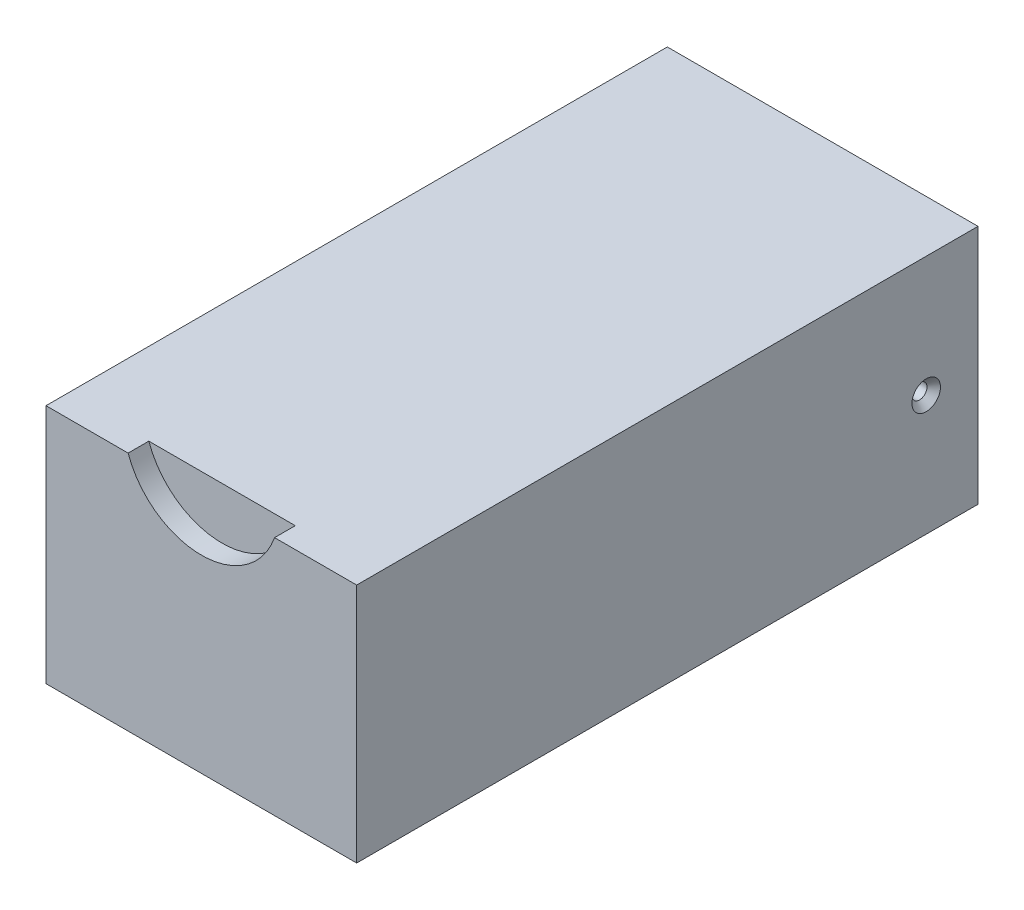
SolidWorks part; units mm, degrees
ref_plane "Plan de face" through (0, 0, 0) normal (0, 0, 1) x (1, 0, 0)
ref_plane "Plan de dessus" through (0, 0, 0) normal (0, 1, 0) x (1, 0, 0)
ref_plane "Plan de droite" through (0, 0, 0) normal (1, 0, 0) x (0, 0, -1)
sketch "Main-Sketch" plane through (0, 0, 0) normal (0, 0, 1) x (1, 0, 0)
  line L1 (-21.4947, -23.25) -> (38.5053, -23.25)
  line L2 (-21.4947, -23.25) -> (-21.4947, 23.25)
  line L3 (-21.4947, 23.25) -> (38.5053, 23.25)
  line L4 (38.5053, -23.25) -> (38.5053, 23.25)
  point P4 (-21.4947, 0)
  dimension "D1" = 60
  dimension "D2" = 46.5
extrude "Main-Extrusion" add sketch "Main-Sketch" along normal blind 120
ref_plane "Plan1" through (0, 0, 112) normal (0, 0, 1) x (1, 0, 0)
sketch "Main-Hole-Sketch" plane through (0, 0, 0) normal (0, 0, -1) x (-1, 0, 0)
  line L0 (-38.5053, -23.25) -> (-38.5053, 23.25) construction
  line L1 (-31.5053, 17.25) -> (14.4947, 17.25)
  line L2 (-31.5053, 17.25) -> (-31.5053, -17.25)
  line L3 (-31.5053, -17.25) -> (14.4947, -17.25)
  line L4 (14.4947, 17.25) -> (14.4947, -17.25)
  line L5 (-38.5053, 23.25) -> (21.4947, 23.25) construction
  line L6 (21.4947, 23.25) -> (21.4947, -23.25) construction
  line L7 (21.4947, -23.25) -> (-38.5053, -23.25) construction
  point P4 (-31.5053, 0)
  point P7 (-38.5053, 0)
  point P8 (-8.5053, 17.25)
  point P11 (-8.5053, 23.25)
  dimension "D1" = 34.5
  dimension "D2" = 46
  dimension "D3" = 7
  dimension "D4" = 7
  dimension "D5" = 6
  dimension "D6" = 6
extrude "Main-Hole" cut sketch "Main-Hole-Sketch" against normal up to surface (112 mm away) up to plane "Plan1"
hole_wizard "Fraisage pour vis à tête fraisée M2.51" positions "Esquisse4" profile "Esquisse3" countersink size "M2.5" standard "Ansi Metric" end condition through all
sketch "Esquisse4" plane through (38.5053, 0, 0) normal (1, 0, 0) x (0, 0, -1)
  line L0 (0, -23.25) -> (0, 23.25) construction
  line L1 (-112, 25.575) -> (-112, -25.575) construction
  point P0 (-10, 0)
  point P3 (0, 0)
  dimension "D2" = 102
sketch "Esquisse3" plane through (38.5053, 0, 10) normal (0, 1, 0) x (0, 0, -1)
  line L0 (0, 0) -> (0, 60)
  line L1 (0, 60) -> (1.45, 60)
  line L2 (1.45, 60) -> (1.45, 1.3)
  line L3 (1.45, 1.3) -> (2.75, 0)
  line L5 (2.75, 0) -> (0, 0)
  line L6 (-1.45, 1.3) -> (-2.75, 0) construction
  line L11 (0, -6.35) -> (0, 107.95) construction
  dimension "Diamètre du perçage jusqu'au prochain" = 2.9
  dimension "Profondeur du perçage jusqu'au prochain" = 60
  dimension "Diamètre du fraisage entrant" = 5.5
  dimension "Angle du fraisage entrant" = 90
sketch "Esquisse5" plane through (0, 0, 120) normal (0, 0, 1) x (1, 0, 0)
  line L0 (38.5053, 23.25) -> (-21.4947, 23.25) construction
  circle A0 centre (8.5053, 28.25) radius 15
  point P4 (8.5053, 23.25)
  dimension "D1" = 30
  dimension "D2" = 5
extrude "Enlèv. mat.-Extru.2" cut sketch "Esquisse5" against normal blind 4
